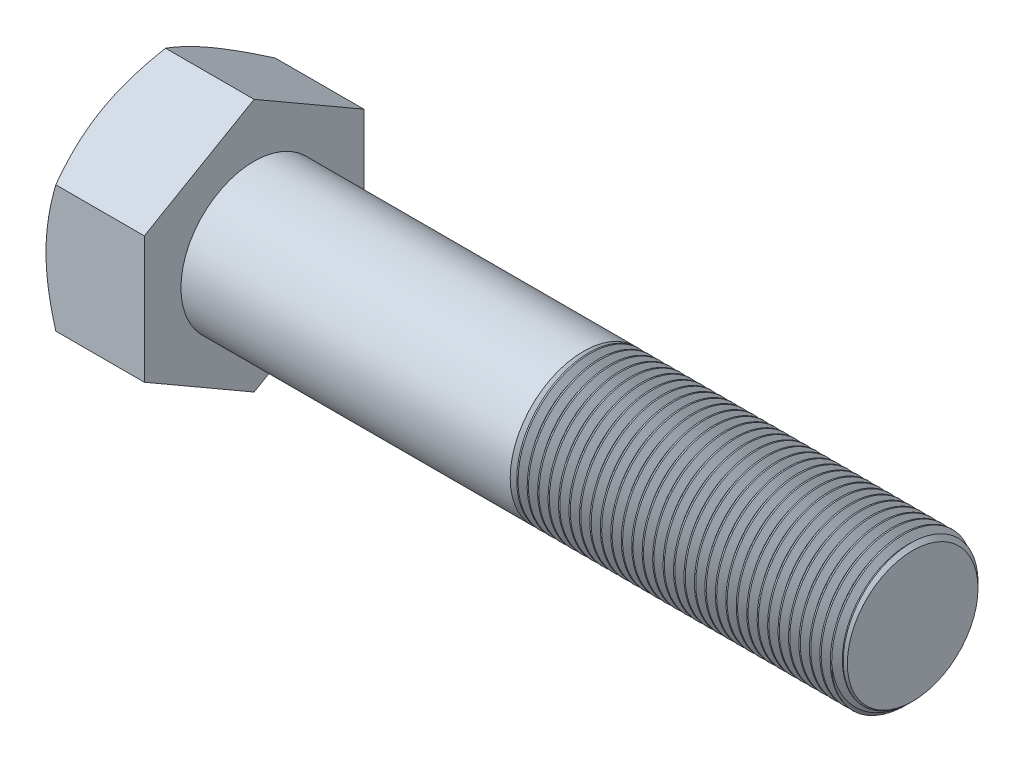
SolidWorks part; units mm, degrees
material "Galvanized Steel"
ref_plane "Front Plane" through (0, 0, 0) normal (0, 0, 1) x (1, 0, 0)
ref_plane "Top Plane" through (0, 0, 0) normal (0, 1, 0) x (1, 0, 0)
ref_plane "Right Plane" through (0, 0, 0) normal (1, 0, 0) x (0, 0, -1)
sketch "Sketch1" plane through (0, 0, 0) normal (0, 0, 1) x (1, 0, 0)
  line L0 (-65.6828, 0) -> (65.6828, 0) construction
  line L1 (65.6828, 12.7) -> (65.6828, -12.7) construction
  line L2 (-48.6172, 19.05) -> (-48.6172, -19.05) construction
  line L3 (-65.6828, 19.05) -> (-65.6828, -19.05) construction
  point P9 (-48.6172, 0)
  point P10 (59.3328, -12.7)
  dimension "Screw Dia" = 25.4
  dimension "Hex" = 38.1
  dimension "Head Ht" = 17.0656
  dimension "Screw Lenght" = 114.3
  dimension "D1" = 6.35
ref_plane "Plane2" through (65.6828, 0, 0) normal (1, 0, 0) x (0, 0, -1)
sketch "Sketch5" plane through (65.6828, 0, 0) normal (1, 0, 0) x (0, 0, -1)
  circle A0 centre (0, 0) radius 12.7
extrude "Boss-Extrude3" add sketch "Sketch5" against normal up to vertex (114.3 mm away) up to point (-48.6172, 0, 0)
sketch "Sketch9" plane through (65.6828, 0, 0) normal (1, 0, 0) x (0, 0, -1)
  circle A1 centre (0, 0) radius 12.7
  circle A2 centre (0, 0) radius 12.7
  dimension "D1" = 0
curve "Helix/Spiral1" pitch 1.8143 height 58.9643 turns 32.5 parameters "Pitch"=1.8143
chamfer "Chamfer1" distance 1.3607 angle 45 1 edges at (65.6828, 0, -12.7)
sketch "Sketch10" plane through (0, 0, 0) normal (0, 0, 1) x (1, 0, 0)
  line L0 (65.6828, 12.7) -> (66.3632, 11.5216)
  line L1 (66.3632, 11.5216) -> (66.59, 11.5216)
  line L2 (66.59, 11.5216) -> (67.2703, 12.7)
  line L3 (65.6828, 12.7) -> (67.2703, 12.7)
  line L4 (66.4766, 12.7) -> (66.4766, 11.5216) construction
  line L5 (66.023, 12.1108) -> (66.9301, 12.1108) construction
  dimension "D1" = 60
  dimension "D2" = 0.2268
  dimension "D3" = 0.9071
sweep "Cut-Sweep1" cut profiles "Sketch10" path "Helix/Spiral1" align with end faces yes
sketch "Sketch11" plane through (0, 0, 0) normal (0, 0, 1) x (1, 0, 0)
  line L0 (-48.6172, 12.7) -> (-48.6172, 0)
  line L1 (-48.6172, 0) -> (21.2328, 0)
  line L3 (21.2328, 0) -> (8.5328, 12.7)
  line L4 (-48.6172, 12.7) -> (8.5328, 12.7)
  dimension "D1" = 45
  dimension "MIn Thread" = 57.15
revolve "Revolve1" add sketch "Sketch11" angle 360 about L1
sketch "Sketch6" plane through (-48.6172, 0, 0) normal (-1, 0, 0) x (0, 0, 1)
  line L0 (0, 19.05) -> (0, -19.05) construction
  line L1 (19.05, 10.9985) -> (0, 21.997)
  line L2 (0, 21.997) -> (-19.05, 10.9985)
  line L3 (-19.05, 10.9985) -> (-19.05, -10.9985)
  line L4 (-19.05, -10.9985) -> (0, -21.997)
  line L5 (0, -21.997) -> (19.05, -10.9985)
  line L6 (19.05, -10.9985) -> (19.05, 10.9985)
  circle A0 centre (0, 0) radius 19.05 construction
extrude "Boss-Extrude4" add sketch "Sketch6" along normal up to vertex (17.0656 mm away) up to point (-65.6828, -19.05, 0)
sketch "Sketch7" plane through (-65.6828, 0, 0) normal (-1, 0, 0) x (0, 0, 1)
  circle A0 centre (0, 0) radius 19.05 construction
  circle A1 centre (0, 0) radius 19.05
sketch "Sketch8" plane through (-65.6828, 0, 0) normal (-1, 0, 0) x (0, 0, 1)
  circle A0 centre (0, 0) radius 19.05 construction
  circle A1 centre (0, 0) radius 19.05
extrude "Cut-Extrude3" cut sketch "Sketch8" against normal through all draft 60 flip side to cut
sketch "Sketch12" plane through (-65.6828, 0, 0) normal (-1, 0, 0) x (0, 0, 1)
  line L0 (0, 14.6685) -> (0, 8.1915) construction
  line L1 (0.5715, 14.6685) -> (0.5715, 8.1915)
  line L2 (-0.5715, 14.6685) -> (-0.5715, 8.1915)
  line L3 (0, 12.7) -> (0, -12.7) construction
  arc A0 (0.5715, 14.6685) -> (-0.5715, 14.6685) centre (0, 14.6685) ccw
  arc A1 (-0.5715, 8.1915) -> (0.5715, 8.1915) centre (0, 8.1915) ccw
  circle A3 centre (0, 0) radius 7.62 construction
  circle A4 centre (0, 0) radius 15.24 construction
  point P2 (0, 11.43)
  dimension "D1" = 15.24
  dimension "D3" = 30.48
  dimension "D2" = 1.143
extrude "Cut-Extrude4" cut sketch "Sketch12" against normal blind 0.254
pattern_circular "CirPattern1" count 3 over 360 about axis through (0, 0, 0) along (1, 0, 0) of "Cut-Extrude4"
equation "\"D2@Sketch10\" = \"Pitch@Helix/Spiral1\"*.125"
equation "\"D3@Sketch10\" = \"Pitch@Helix/Spiral1\"*.5"
equation "\"D3@Helix/Spiral1\" = \"MIn Thread@Sketch11\"+\"Pitch@Helix/Spiral1\""
equation "\"D1@Chamfer1\" = \"Pitch@Helix/Spiral1\"*.75"
equation "\"D1@Sketch12\" = \"Hex@Sketch1\"*.4"
equation "\"D3@Sketch12\" = \"Hex@Sketch1\"*.8"
equation "\"D2@Sketch12\" = \"Hex@Sketch1\"*.03"
equation "\"D1@Sketch1\" = \"Pitch@Helix/Spiral1\"*3.5"
